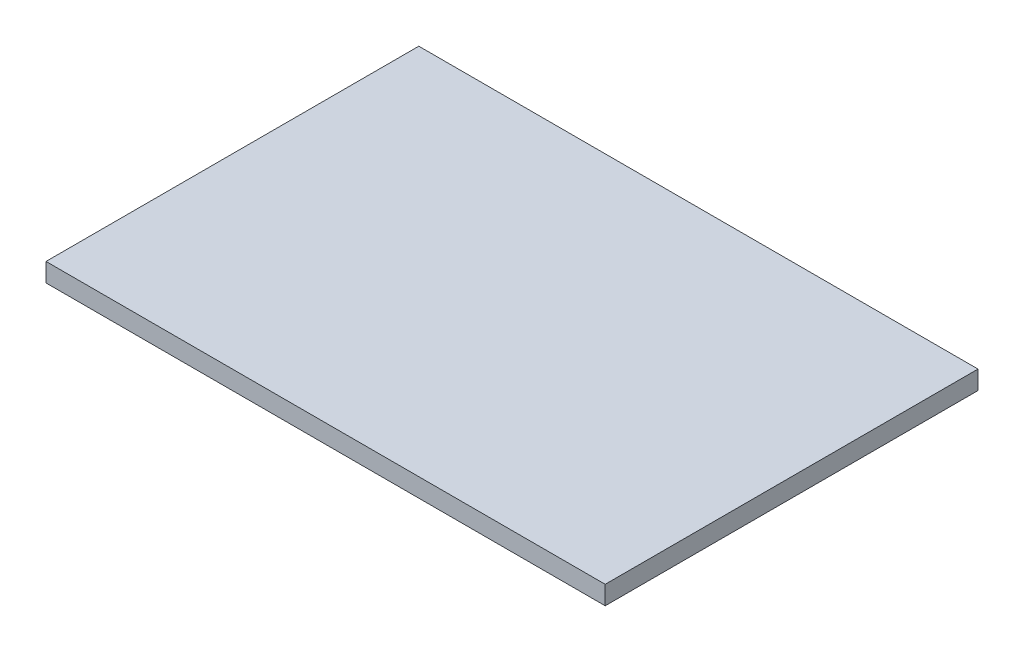
SolidWorks part; units mm, degrees
ref_plane "Ebene vorne" through (0, 0, 0) normal (0, 0, 1) x (1, 0, 0)
ref_plane "Ebene oben" through (0, 0, 0) normal (0, 1, 0) x (1, 0, 0)
ref_plane "Ebene rechts" through (0, 0, 0) normal (1, 0, 0) x (0, 0, -1)
sketch "Skizze1" plane through (0, 0, 0) normal (0, 1, 0) x (1, 0, 0)
  line L0 (0, 0) -> (60, 0)
  line L1 (-2.2, 0) -> (2.2, 0) construction
  line L2 (60, 0) -> (60, 40)
  line L3 (60, 40) -> (0, 40)
  line L4 (0, -2.2) -> (0, 2.2) construction
  line L5 (0, 40) -> (0, 0)
  dimension "D1" = 40
  dimension "D2" = 60
extrude "Aufsatz-Linear austragen1" add sketch "Skizze1" along normal blind 2
